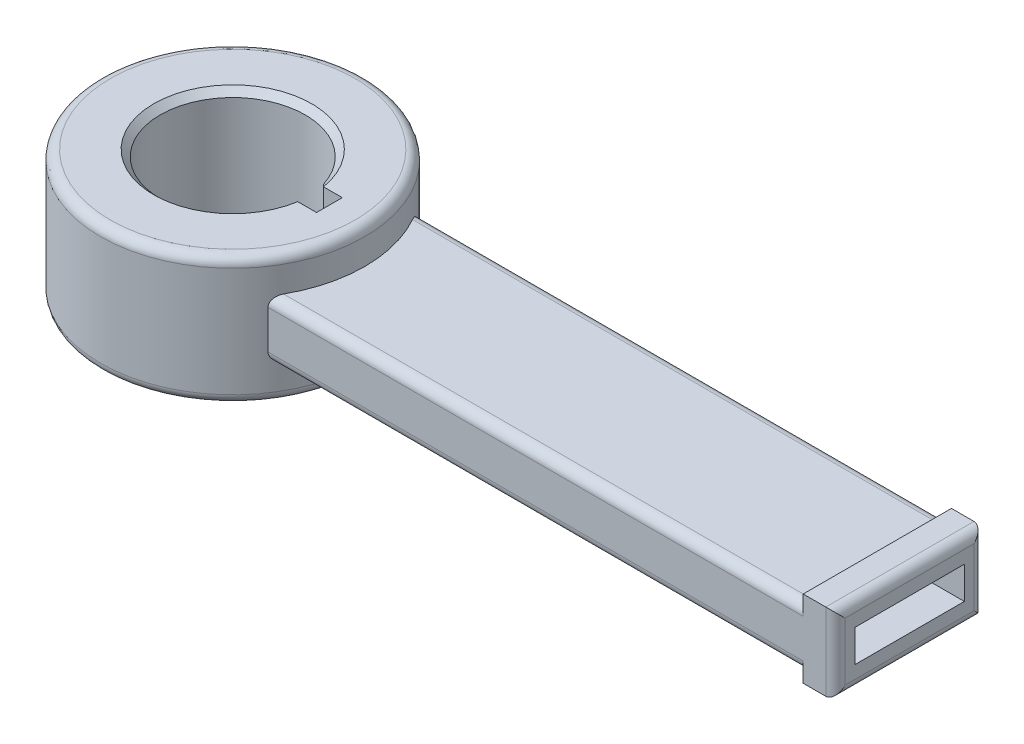
SolidWorks part; units mm, degrees
ref_plane "前视基准面" through (0, 0, 0) normal (0, 0, 1) x (1, 0, 0)
ref_plane "上视基准面" through (0, 0, 0) normal (0, 1, 0) x (1, 0, 0)
ref_plane "右视基准面" through (0, 0, 0) normal (1, 0, 0) x (0, 0, -1)
other "Configuration Table"
sketch "草图1" plane through (0, 0, 0) normal (0, 1, 0) x (1, 0, 0)
  circle A0 centre (0, 0) radius 41
  circle A1 centre (0, 0) radius 22.5
  dimension "D1" = 82
  dimension "D2" = 45
extrude "凸台-拉伸1" add sketch "草图1" along normal blind 40
ref_plane "基准面1" through (200, 0, 0) normal (1, 0, 0) x (0, 0, -1)
sketch "草图2" plane through (200, 0, 0) normal (1, 0, 0) x (0, 0, -1)
  line L0 (-41, 20) -> (41, 20) construction
  line L1 (-41, 40) -> (-41, 0) construction
  line L2 (0, 40) -> (0, 0) construction
  line L3 (41, 40) -> (-41, 40) construction
  line L4 (41, 0) -> (41, 40) construction
  line L6 (-23, 8) -> (23, 8)
  line L7 (-23, 8) -> (-23, 32)
  line L8 (-23, 32) -> (23, 32)
  line L9 (23, 8) -> (23, 32)
  line L10 (-23, 8) -> (23, 32) construction
  line L11 (-23, 32) -> (23, 8) construction
  point P11 (0, 20)
  dimension "D1" = 46
  dimension "D2" = 24
extrude "凸台-拉伸2" add sketch "草图2" along normal blind 10 separate body
sketch "草图3" plane through (200, 0, 0) normal (1, 0, 0) x (0, 0, -1)
  line L0 (-23, 20) -> (23, 20) construction
  line L1 (-23, 32) -> (-23, 8) construction
  line L2 (23, 8) -> (23, 32) construction
  line L3 (0, 32) -> (0, 8) construction
  line L4 (23, 32) -> (-23, 32) construction
  line L5 (-23, 8) -> (23, 8) construction
  line L7 (-23, 11) -> (23, 11)
  line L8 (-23, 11) -> (-23, 29)
  line L9 (-23, 29) -> (23, 29)
  line L10 (23, 11) -> (23, 29)
  line L11 (-23, 11) -> (23, 29) construction
  line L12 (-23, 29) -> (23, 11) construction
  point P12 (0, 20)
  dimension "D1" = 18
extrude "凸台-拉伸3" add sketch "草图3" against normal up to surface (166.0589 mm away)
sketch "草图4" plane through (0, 0, 0) normal (0, 1, 0) x (1, 0, 0)
  line L0 (0, 0) -> (259.6062, 0) construction
  line L2 (-10.1006, 4) -> (30, 4)
  line L3 (-10.1006, 4) -> (-10.1006, -4)
  line L4 (-10.1006, -4) -> (30, -4)
  line L5 (30, 4) -> (30, -4)
  line L6 (-10.1006, 4) -> (30, -4) construction
  line L7 (-10.1006, -4) -> (30, 4) construction
  point P3 (9.9497, 0)
  dimension "D1" = 8
  dimension "D2" = 30
extrude "切除-拉伸1" cut sketch "草图4" along normal through all
sketch "草图5" plane through (200, 0, 0) normal (1, 0, 0) x (0, 0, -1)
  line L0 (-23, 20) -> (23, 20) construction
  line L1 (-23, 32) -> (-23, 8) construction
  line L2 (23, 11) -> (23, 29) construction
  line L3 (0, 32) -> (0, 8) construction
  line L4 (23, 32) -> (-23, 32) construction
  line L5 (-23, 8) -> (23, 8) construction
  line L7 (-17, 15) -> (17, 15)
  line L8 (-17, 15) -> (-17, 25)
  line L9 (-17, 25) -> (17, 25)
  line L10 (17, 15) -> (17, 25)
  line L11 (-17, 15) -> (17, 25) construction
  line L12 (-17, 25) -> (17, 15) construction
  point P12 (0, 20)
  dimension "D1" = 34
  dimension "D2" = 10
extrude "切除-拉伸2" cut sketch "草图5" against normal mid plane 20
fillet "圆角1" radius 3 10 edges at (210, 20, -23) (210, 8, 0) (210, 32, 0) (210, 20, 23) (116.9706, 11, -23) (116.9706, 29, -23) (116.9706, 11, 23) (116.9706, 29, 23) (0, 0, 41) (0, 40, 41)
chamfer "倒角1" distance 2 angle 45 4 edges at (22.1416, 20, 4) (-22.5, 40, 0) (22.1416, 20, -4) (-22.5, 0, 0)
